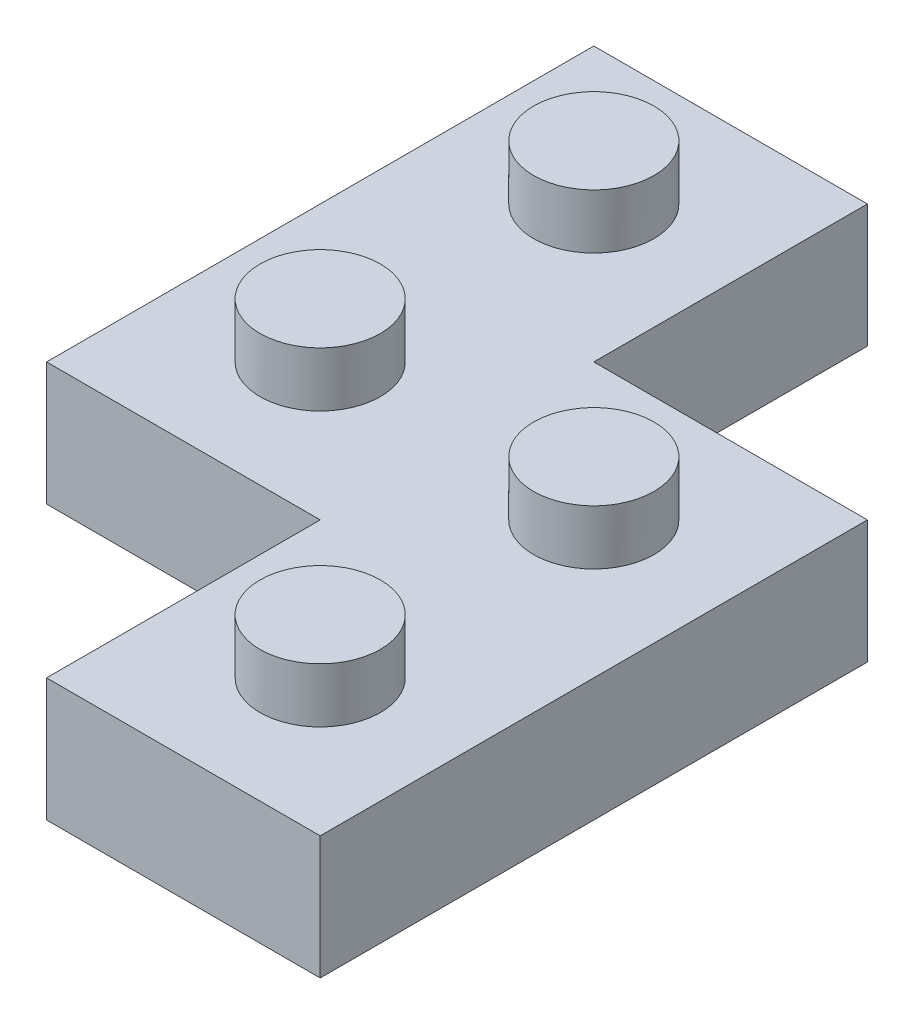
SolidWorks part; units mm, degrees
material "ABS"
ref_plane "Front Plane" through (0, 0, 0) normal (0, 0, 1) x (1, 0, 0)
ref_plane "Top Plane" through (0, 0, 0) normal (0, 1, 0) x (1, 0, 0)
ref_plane "Right Plane" through (0, 0, 0) normal (1, 0, 0) x (0, 0, -1)
sketch "Sketch1" plane through (0, 0, 0) normal (0, 1, 0) x (1, 0, 0)
  line L0 (-5.6746, 20.3112) -> (7.0254, 20.3112)
  line L1 (7.0254, 20.3112) -> (7.0254, 7.6112)
  line L2 (7.0254, 7.6112) -> (19.7254, 7.6112)
  line L3 (19.7254, 7.6112) -> (19.7254, -17.7888)
  line L4 (19.7254, -17.7888) -> (7.0254, -17.7888)
  line L5 (7.0254, -17.7888) -> (7.0254, -5.0888)
  line L6 (7.0254, -5.0888) -> (-5.6746, -5.0888)
  line L7 (-5.6746, -5.0888) -> (-5.6746, 20.3112)
  dimension "D1" = 38.1
  dimension "D2" = 12.7
  dimension "D3" = 12.7
  dimension "D4" = 12.7
  dimension "D5" = 12.7
extrude "Boss-Extrude1" add sketch "Sketch1" along normal blind 5.715
sketch "Sketch2" plane through (0, 5.715, 0) normal (0, 1, 0) x (1, 0, 0)
  line L0 (-5.6746, 20.3112) -> (-5.6746, -5.0888) construction
  line L1 (19.7254, -17.7888) -> (19.7254, 7.6112) construction
  line L2 (7.0254, 20.3112) -> (-5.6746, 20.3112) construction
  circle A0 centre (0.6754, 1.2612) radius 2.794
  circle A1 centre (13.3754, 1.2612) radius 2.794
  circle A2 centre (0.6754, 13.9612) radius 2.794
  circle A3 centre (13.3754, -11.4388) radius 2.794
  dimension "D2" = 6.35
  dimension "D4" = 6.35
  dimension "D5" = 12.7
  dimension "D3" = 6.35
  dimension "D6" = 12.7
  dimension "D1" = 2
extrude "Boss-Extrude3" add sketch "Sketch2" along normal blind 2.54
